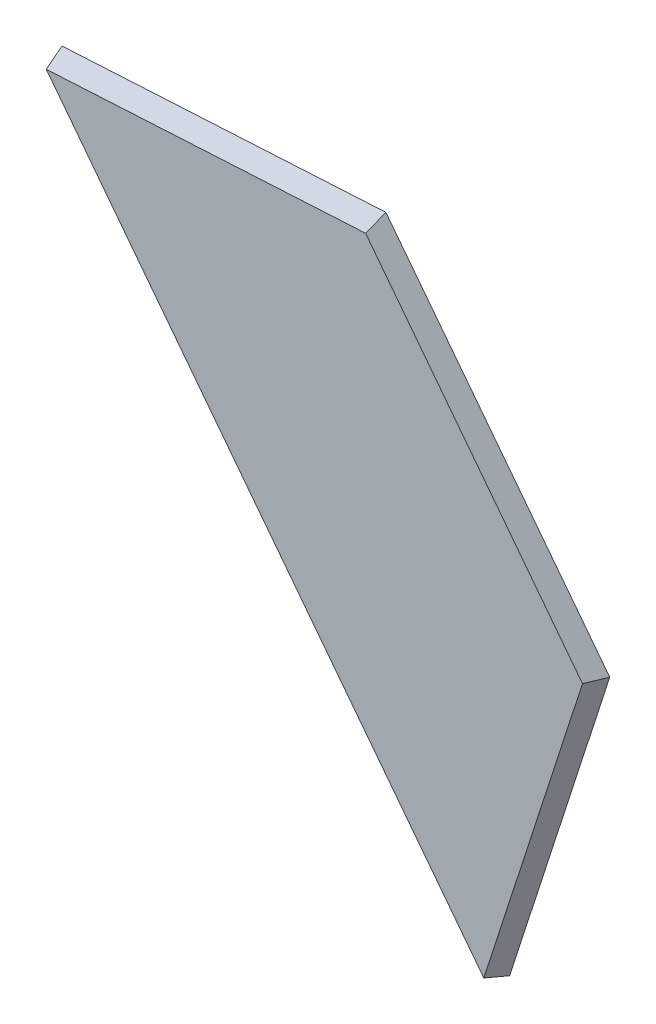
SolidWorks part; units mm, degrees
ref_plane "Спереди" through (0, 0, 0) normal (0, 0, 1) x (1, 0, 0)
ref_plane "Сверху" through (0, 0, 0) normal (0, 1, 0) x (1, 0, 0)
ref_plane "Справа" through (0, 0, 0) normal (1, 0, 0) x (0, 0, -1)
sketch "Эскиз1" plane through (0, 0, 0) normal (0, 0, 1) x (1, 0, 0)
  line L0 (-849.5899, 515.839) -> (787.506, 606.4051)
  line L1 (787.506, 606.4051) -> (281.6156, -953.1975)
  line L2 (281.6156, -953.1975) -> (-849.5899, 515.839)
extrude "Бобышка-Вытянуть1" add sketch "Эскиз1" along normal blind 60
chamfer "Chamfer3" distance 60 angle 11.23 1 edges at (-31.0419, 561.122, 60) first distance on face at (-31.0419, 561.122, 30)
chamfer "Chamfer4" distance 60 angle 11.23 1 edges at (532.5904, -179.4708, 60) first distance on face at (533.5756, -176.4335, 30)
chamfer "Chamfer5" distance 60 angle 9.015 1 edges at (-283.9872, -218.6793, 60) first distance on face at (-283.9872, -218.6793, 30)
sketch "Sketch1" plane through (0, 0, 0) normal (0, 0, -1) x (-1, 0, 0)
  line L0 (-534.5608, -173.3962) -> (31.0419, 561.122)
  line L1 (-281.6156, -953.1975) -> (-787.506, 606.4051) construction
  line L2 (-787.506, 606.4051) -> (849.5899, 515.839) construction
  line L3 (31.0419, 561.122) -> (-787.506, 606.4051)
  line L4 (-787.506, 606.4051) -> (-534.5608, -173.3962)
extrude "Cut-Extrude1" cut sketch "Sketch1" against normal through all
equation "\"D1@Бобышка-Вытянуть1\" = \"THI@Geocorkwithdoor1.0.Assembly\""
equation "\"DC1@Chamfer\" = \"THI@Geocorkwithdoor1.0.Assembly\""
equation "\"DC2@Chamfer\" = \"AAchanferangle@Geocorkwithdoor1.0.Assembly\""
equation "\"DC2@Chamfer\" = \"ABchanferAngle@Geocorkwithdoor1.0.Assembly\""
equation "\"D2@Chamfer3\" = \"ABchanferAngle@Geocorkwithdoor1.0.Assembly\""
equation "\"D2@Chamfer4\" = \"ABchanferAngle@Geocorkwithdoor1.0.Assembly\""
